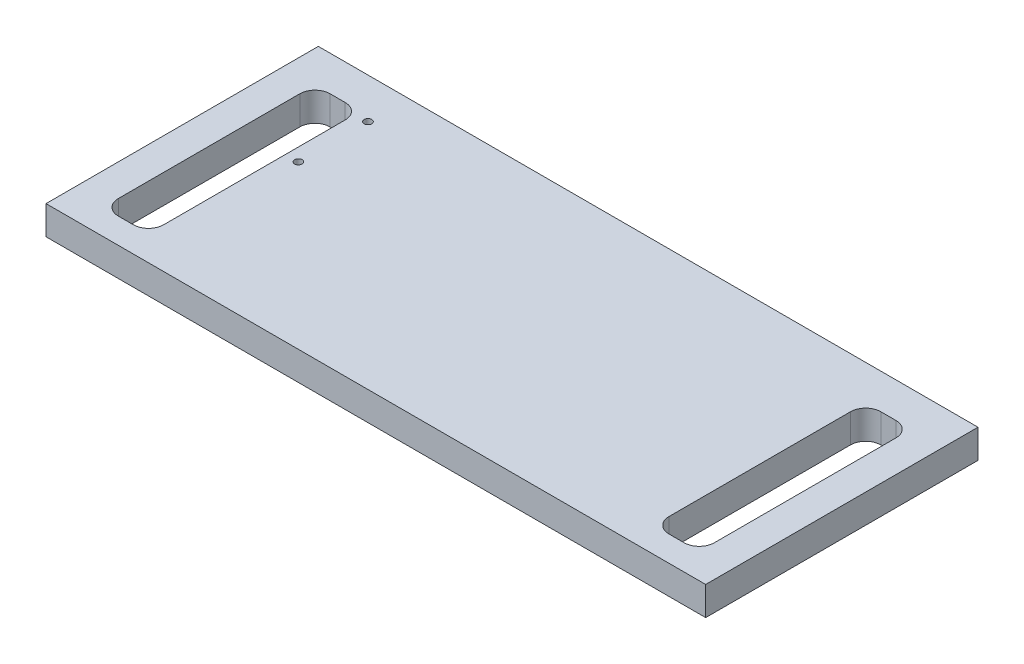
SolidWorks part; units mm, degrees
ref_plane "前视基准面" through (0, 0, 0) normal (0, 0, 1) x (1, 0, 0)
ref_plane "上视基准面" through (0, 0, 0) normal (0, 1, 0) x (1, 0, 0)
ref_plane "右视基准面" through (0, 0, 0) normal (1, 0, 0) x (0, 0, -1)
sketch "草图1" plane through (0, 0, 0) normal (0, 1, 0) x (1, 0, 0)
  line L1 (-109, 45) -> (109, 45)
  line L2 (-109, 45) -> (-109, -45)
  line L3 (-109, -45) -> (109, -45)
  line L4 (109, 45) -> (109, -45)
  line L5 (-109, 45) -> (109, -45) construction
  line L6 (-109, -45) -> (109, 45) construction
  point P0 (0, 0)
  dimension "D1" = 218
  dimension "D2" = 90
extrude "凸台-拉伸1" add sketch "草图1" along normal blind 9.5
sketch "草图2" plane through (0, 9.5, 0) normal (0, 1, 0) x (1, 0, 0)
  line L0 (-109, 45) -> (-109, -45) construction
  line L1 (-83.5, -36.6231) -> (-98.5, -36.6231)
  line L2 (-83.5, -36.6231) -> (-83.5, 33.3769)
  line L3 (-83.5, 33.3769) -> (-98.5, 33.3769)
  line L4 (-98.5, -36.6231) -> (-98.5, 33.3769)
  line L5 (-83.5, -36.6231) -> (-98.5, 33.3769) construction
  line L6 (-83.5, 33.3769) -> (-98.5, -36.6231) construction
  line L7 (109, -45) -> (109, 45) construction
  line L8 (83.5, -36.6231) -> (98.5, -36.6231)
  line L9 (83.5, -36.6231) -> (83.5, 33.3769)
  line L10 (83.5, 33.3769) -> (98.5, 33.3769)
  line L11 (98.5, -36.6231) -> (98.5, 33.3769)
  point P0 (-91, -1.6231)
  dimension "D1" = 15
  dimension "D2" = 70
  dimension "D3" = 10.5
  dimension "D4" = 15
  dimension "D5" = 10.5
  dimension "D6" = 70
extrude "切除-拉伸1" cut sketch "草图2" against normal through all
fillet "圆角1" radius 5 4 edges at (-98.5, 4.75, 36.6231) (-83.5, 4.75, 36.6231) (-83.5, 4.75, -33.3769) (-98.5, 4.75, -33.3769)
fillet "圆角2" radius 5 4 edges at (98.5, 4.75, -33.3769) (83.5, 4.75, -33.3769) (83.5, 4.75, 36.6231) (98.5, 4.75, 36.6231)
sketch "草图3" plane through (0, 9.5, 0) normal (0, 1, 0) x (1, 0, 0)
  line L0 (-84, 8.65) -> (-74.5, 8.65) construction
  line L1 (-74.5, 31.65) -> (-84, 31.65) construction
  circle A0 centre (-79.25, 8.65) radius 1.25
  circle A1 centre (-79.25, 31.65) radius 1.25
  dimension "D1" = 2.5
extrude "切除-拉伸2" cut sketch "草图3" against normal through all
